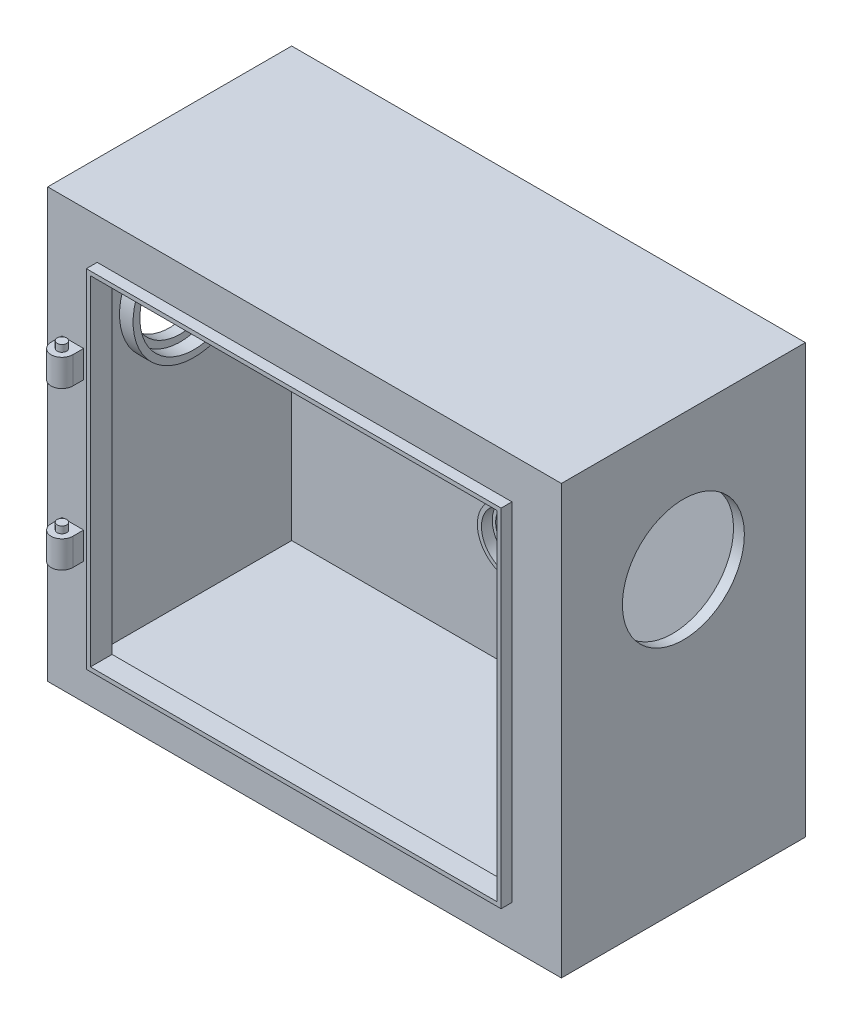
SolidWorks part; units mm, degrees
ref_plane "Alzado" through (0, 0, 0) normal (0, 0, 1) x (1, 0, 0)
ref_plane "Planta" through (0, 0, 0) normal (0, 1, 0) x (1, 0, 0)
ref_plane "Vista lateral" through (0, 0, 0) normal (1, 0, 0) x (0, 0, -1)
sketch "Croquis1" plane through (0, 0, 0) normal (0, 0, 1) x (1, 0, 0)
  line L0 (-189.5, 158) -> (189.5, 158)
  line L1 (-181.5, -150) -> (181.5, -150) construction
  line L2 (-181.5, -150) -> (-181.5, 150) construction
  line L3 (-181.5, 150) -> (181.5, 150) construction
  line L4 (181.5, -150) -> (181.5, 150) construction
  line L5 (-181.5, -150) -> (181.5, 150) construction
  line L6 (-181.5, 150) -> (181.5, -150) construction
  line L7 (189.5, -158) -> (189.5, 158)
  line L8 (-189.5, -158) -> (189.5, -158)
  line L9 (-189.5, -158) -> (-189.5, 158)
  point P0 (0, 0)
  dimension "D1" = 363
  dimension "D2" = 300
  dimension "D3" = 8
extrude "Saliente-Extruir1" add sketch "Croquis1" along normal blind 180
shell "Vaciado1" thickness 8 removed face at (0, 0, 180)
sketch "Croquis2" plane through (-189.5, 0, 0) normal (-1, 0, 0) x (0, 0, 1)
  line L0 (0, 158) -> (90, 158) construction
  line L1 (180, 158) -> (0, 158) construction
  circle A0 centre (90, 58) radius 35
extrude "Cortar-Extruir4" cut sketch "Croquis2" against normal blind 20 contours A0
sketch "Croquis4" plane through (-181.5, 0, 0) normal (1, 0, 0) x (0, 0, -1)
  circle A1 centre (-90, 58) radius 40
  circle A2 centre (-90, 58) radius 45
extrude "Saliente-Extruir4" add sketch "Croquis4" along normal blind 10
sketch "Croquis6" plane through (189.5, 0, 0) normal (1, 0, 0) x (0, 0, -1)
  line L0 (-90, 158) -> (-90, 58) construction
  line L1 (-180, 158) -> (0, 158) construction
  circle A0 centre (-90, 58) radius 45
  dimension "D1" = 90
extrude "Cortar-Extruir6" cut sketch "Croquis6" against normal blind 10 contours A0
sketch "Croquis7" plane through (0, 0, 8) normal (0, 0, 1) x (1, 0, 0)
  circle A3 centre (-2.5, -53) radius 21
  circle A4 centre (-2.5, -53) radius 24
  dimension "D1" = 42
  dimension "D2" = 48
extrude "Saliente-Extruir9" add sketch "Croquis7" along normal blind 18
ref_plane "Plano6" through (0, 0, 180) normal (0, 0, 1) x (1, 0, 0)
sketch "Croquis11" plane through (0, 0, 180) normal (0, 0, 1) x (1, 0, 0)
  line L1 (181.5, 150) -> (-181.5, 150)
  line L2 (181.5, 150) -> (181.5, -150)
  line L3 (181.5, -150) -> (-181.5, -150)
  line L4 (-181.5, 150) -> (-181.5, -150)
  line L5 (181.5, 150) -> (-181.5, -150) construction
  line L6 (181.5, -150) -> (-181.5, 150) construction
  line L7 (-150, 125) -> (150, 125)
  line L8 (-150, 125) -> (-150, -125)
  line L9 (-150, -125) -> (150, -125)
  line L10 (150, 125) -> (150, -125)
  line L11 (-150, 125) -> (150, -125) construction
  line L12 (-150, -125) -> (150, 125) construction
  point P0 (0, 0)
  point P7 (0, 0)
  dimension "D1" = 300
  dimension "D2" = 250
extrude "Saliente-Extruir10" add sketch "Croquis11" against normal blind 8
sketch "Croquis12" plane through (0, 0, 180) normal (0, 0, 1) x (1, 0, 0)
  line L1 (150, -125) -> (-150, -125)
  line L2 (150, -125) -> (150, 125)
  line L3 (150, 125) -> (-150, 125)
  line L4 (-150, -125) -> (-150, 125)
  line L5 (150, -125) -> (-150, 125) construction
  line L6 (150, 125) -> (-150, -125) construction
  line L7 (153, -128) -> (-153, -128)
  line L8 (153, -128) -> (153, 128)
  line L9 (153, 128) -> (-153, 128)
  line L10 (-153, -128) -> (-153, 128)
  line L11 (153, -128) -> (-153, 128) construction
  line L12 (153, 128) -> (-153, -128) construction
  point P0 (0, 0)
  point P8 (0, 0)
  dimension "D1" = 3
  dimension "D2" = 3
extrude "Saliente-Extruir11" add sketch "Croquis12" along normal blind 8
sketch "Croquis13" plane through (0, 0, 180) normal (0, 0, 1) x (1, 0, 0)
  line L0 (189.5, 158) -> (-189.5, 158) construction
  line L1 (-179, 68) -> (-163, 68)
  line L2 (-179, 68) -> (-179, 48)
  line L3 (-179, 48) -> (-163, 48)
  line L4 (-163, 68) -> (-163, 48)
  line L5 (-179, 68) -> (-163, 48) construction
  line L6 (-179, 48) -> (-163, 68) construction
  line L7 (-153, 128) -> (-153, -128) construction
  point P0 (-171, 58)
  dimension "D1" = 100
  dimension "D2" = 20
  dimension "D3" = 16
  dimension "D4" = 10
extrude "Saliente-Extruir13" add sketch "Croquis13" along normal blind 8
sketch "Croquis14" plane through (0, 68, 0) normal (0, 1, 0) x (1, 0, 0)
  line L0 (-163, -188) -> (-179, -188) construction
  line L1 (-179, -188) -> (-163, -188)
  arc A0 (-179, -188) -> (-163, -188) centre (-171, -188) ccw
extrude "Saliente-Extruir14" add sketch "Croquis14" against normal blind 20
sketch "Croquis15" plane through (0, 68, 0) normal (0, 1, 0) x (1, 0, 0)
  circle A0 centre (-171, -188) radius 3.5
  arc A1 (-179, -188) -> (-163, -188) centre (-171, -188) ccw construction
  dimension "D1" = 7
extrude "Saliente-Extruir15" add sketch "Croquis15" along normal blind 5
sketch "Croquis17" plane through (0, 0, 180) normal (0, 0, 1) x (1, 0, 0)
  line L1 (-153, 128) -> (-153, -128) construction
  line L2 (-179, -48) -> (-163, -48)
  line L3 (-179, -48) -> (-179, -68)
  line L4 (-179, -68) -> (-163, -68)
  line L5 (-163, -48) -> (-163, -68)
  line L6 (-179, -48) -> (-163, -68) construction
  line L7 (-179, -68) -> (-163, -48) construction
  line L8 (-189.5, -158) -> (189.5, -158) construction
  point P2 (-171, -58)
  dimension "D1" = 20
  dimension "D2" = 16
  dimension "D3" = 10
  dimension "D4" = 100
extrude "Saliente-Extruir16" add sketch "Croquis17" along normal blind 8
sketch "Croquis18" plane through (0, -48, 0) normal (0, 1, 0) x (1, 0, 0)
  line L0 (-179, -188) -> (-163, -188)
  arc A0 (-179, -188) -> (-163, -188) centre (-171, -188) ccw
extrude "Saliente-Extruir17" add sketch "Croquis18" against normal blind 20
sketch "Croquis19" plane through (0, -48, 0) normal (0, 1, 0) x (1, 0, 0)
  circle A0 centre (-171, -188) radius 3.5
  arc A1 (-179, -188) -> (-163, -188) centre (-171, -188) ccw construction
  dimension "D1" = 7
extrude "Saliente-Extruir18" add sketch "Croquis19" along normal blind 5
sketch "Croquis20" plane through (0, 0, 8) normal (0, 0, 1) x (1, 0, 0)
  circle A0 centre (-2.5, -53) radius 18.5
  circle A1 centre (-2.5, -53) radius 21
  circle A2 centre (-2.5, -53) radius 21 construction
  dimension "D1" = 37
extrude "Saliente-Extruir19" add sketch "Croquis20" along normal blind 10
